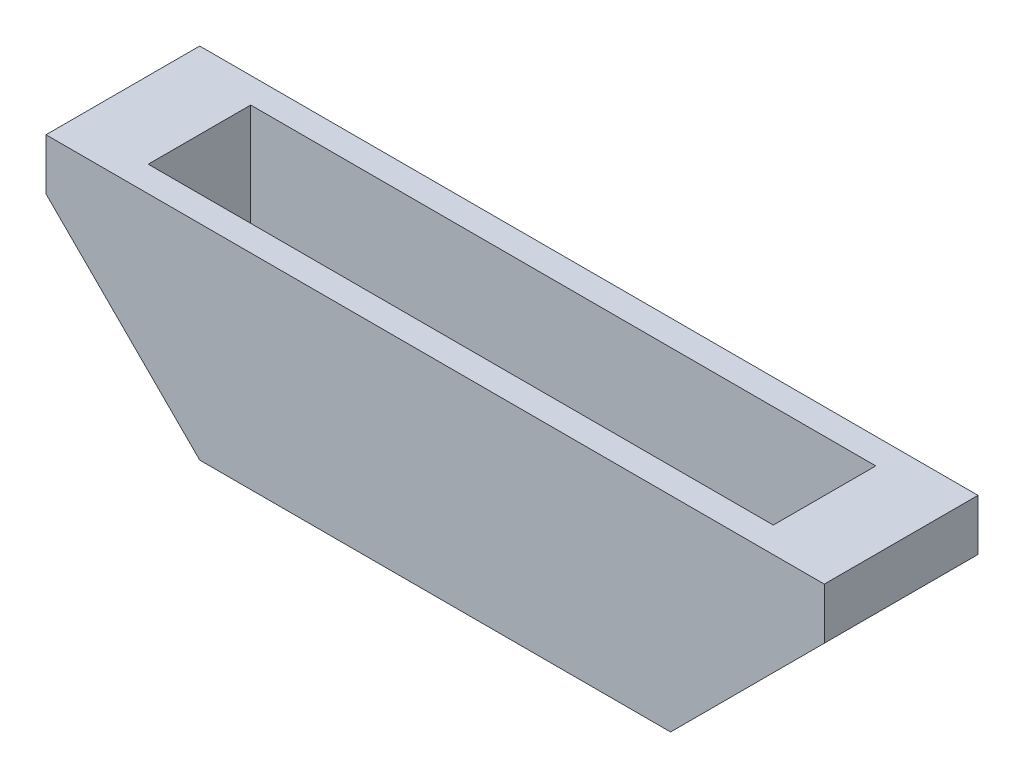
SolidWorks part; units mm, degrees
ref_plane "Front Plane" through (0, 0, 0) normal (0, 0, 1) x (1, 0, 0)
ref_plane "Top Plane" through (0, 0, 0) normal (0, 1, 0) x (1, 0, 0)
ref_plane "Right Plane" through (0, 0, 0) normal (1, 0, 0) x (0, 0, -1)
sketch "Sketch1" plane through (0, 0, 0) normal (0, 1, 0) x (1, 0, 0)
  line L1 (-77.47, -12.7) -> (77.47, -12.7)
  line L2 (-77.47, -12.7) -> (-77.47, 12.7)
  line L3 (-77.47, 12.7) -> (77.47, 12.7)
  line L4 (77.47, -12.7) -> (77.47, 12.7)
  line L5 (-77.47, -12.7) -> (77.47, 12.7) construction
  line L6 (-77.47, 12.7) -> (77.47, -12.7) construction
  line L7 (-96.4606, -19.05) -> (96.4606, -19.05)
  line L8 (-96.4606, -19.05) -> (-96.4606, 19.05)
  line L9 (-96.4606, 19.05) -> (96.4606, 19.05)
  line L10 (96.4606, -19.05) -> (96.4606, 19.05)
  line L11 (-96.4606, -19.05) -> (96.4606, 19.05) construction
  line L12 (-96.4606, 19.05) -> (96.4606, -19.05) construction
  point P0 (0, 0)
  point P6 (0, 0)
  dimension "D1" = 25.4
  dimension "D2" = 154.94
  dimension "D3" = 38.1
extrude "Boss-Extrude4" add sketch "Sketch1" against normal blind 50.8 contours L7 L10 L9 L8 L4 L1 L2 L3 | L1 L4 L3 L2 | L8 L7 L10 L9 region at (0, 0, 0) region at (-94.4941, 0, 0)
chamfer "Chamfer2" distance 38.1 angle 45 2 edges at (96.4606, -50.8, 0) (-96.4606, -50.8, 0)
extrude "Cut-Extrude1" cut sketch "Sketch1<5>" against normal blind 35.56 contours L1 L4 L3 L2 region at (0, 0, 0)
sketch "Sketch1<5>" plane through (0, 0, 0) normal (0, 1, 0) x (1, 0, 0) same geometry as "Sketch1"
